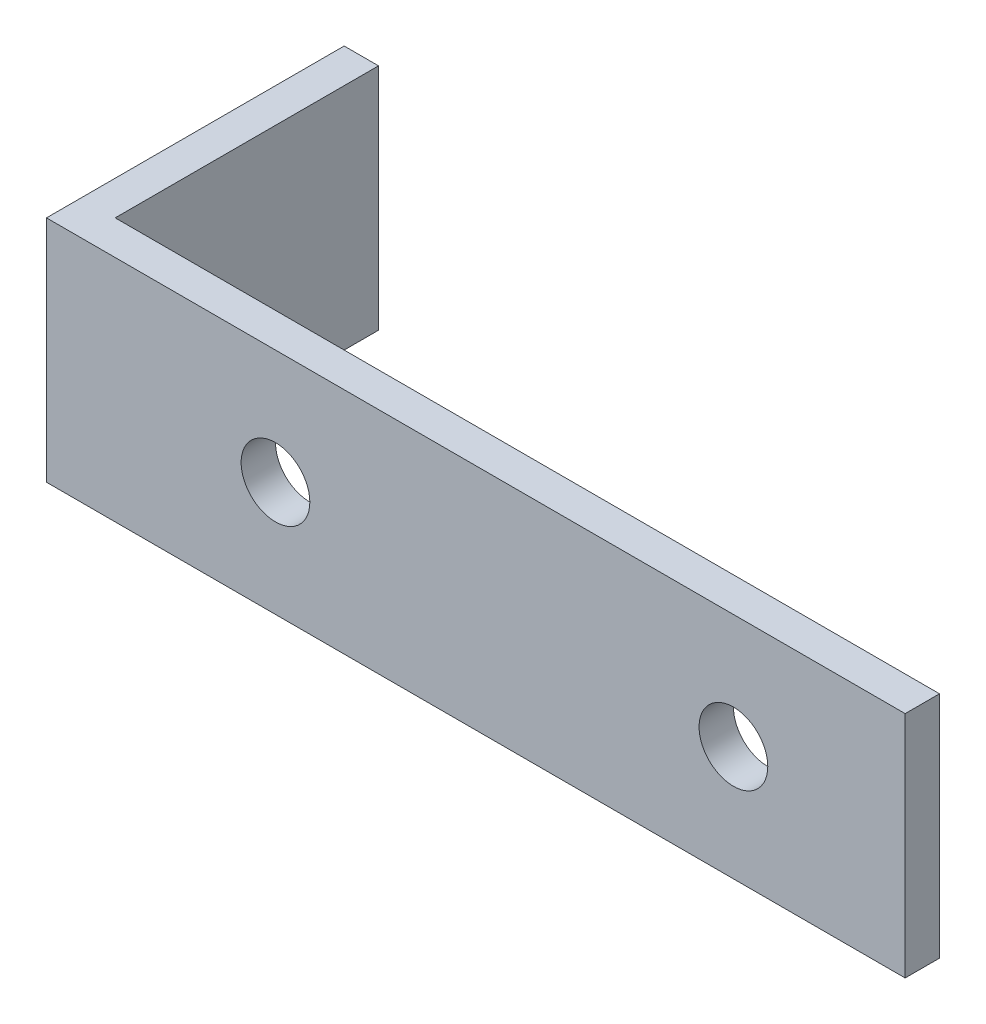
SolidWorks part; units mm, degrees
ref_plane "Front Plane" through (0, 0, 0) normal (0, 0, 1) x (1, 0, 0)
ref_plane "Top Plane" through (0, 0, 0) normal (0, 1, 0) x (1, 0, 0)
ref_plane "Right Plane" through (0, 0, 0) normal (1, 0, 0) x (0, 0, -1)
sketch "Sketch1" plane through (0, 0, 0) normal (0, 0, 1) x (1, 0, 0)
  line L1 (0, 0) -> (75, 0)
  line L2 (0, 0) -> (0, 20)
  line L3 (0, 20) -> (75, 20)
  line L4 (75, 0) -> (75, 20)
  line L5 (0, 0) -> (3, 0)
  line L6 (0, 0) -> (0, 20)
  line L7 (0, 20) -> (3, 20)
  line L8 (3, 0) -> (3, 20)
  circle A0 centre (60, 10) radius 3
  circle A1 centre (20, 10) radius 3
  dimension "D4" = 6
  dimension "D7" = 6
  dimension "D1" = 75
  dimension "D2" = 20
  dimension "D3" = 15
  dimension "D5" = 10
  dimension "D6" = 40
  dimension "D8" = 10
  dimension "D9" = 20
  dimension "D10" = 3
extrude "Boss-Extrude2" add sketch "Sketch1" along normal blind 3 contours L1 L8 L3 L2 | L8 L1 L4 L3 A1 A0 region at (1.5, 10, 0) region at (38.9591, 10, 0)
extrude "Boss-Extrude3" add sketch "Sketch1<3>" against normal blind 23 contours L1 L8 L3 L2 region at (1.5, 10, 0)
sketch "Sketch1<3>" plane through (0, 0, 0) normal (0, 0, 1) x (1, 0, 0) same geometry as "Sketch1"
sketch "Sketch2" plane through (3, 0, 0) normal (1, 0, 0) x (0, 0, -1)
  line L0 (23, 0) -> (0, 0) construction
  line L1 (23, 20) -> (20, 20)
  line L2 (23, 20) -> (23, 0)
  line L3 (23, 0) -> (20, 0)
  line L4 (20, 20) -> (20, 0)
  dimension "D1" = 3
